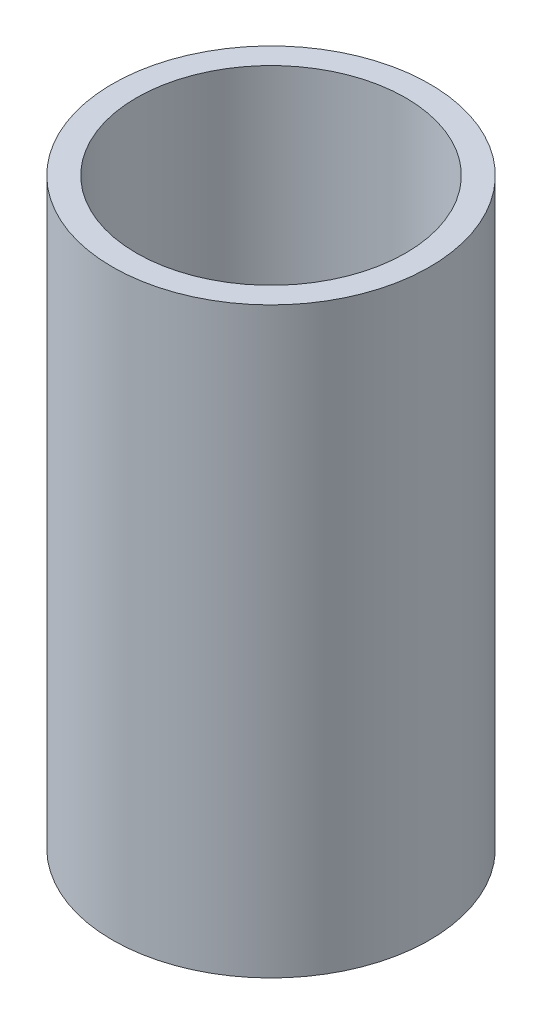
SolidWorks part; units mm, degrees
ref_plane "Front Plane" through (0, 0, 0) normal (0, 0, 1) x (1, 0, 0)
ref_plane "Top Plane" through (0, 0, 0) normal (0, 1, 0) x (1, 0, 0)
ref_plane "Right Plane" through (0, 0, 0) normal (1, 0, 0) x (0, 0, -1)
sketch "Sketch1" plane through (0, 0, 0) normal (0, 1, 0) x (1, 0, 0)
  circle A0 centre (0, 0) radius 45
  dimension "SLEEVE_OD" = 90
extrude "Boss-Extrude1" add sketch "Sketch1" along normal blind 165.384
sketch "Sketch2" plane through (0, 0, 0) normal (0, 1, 0) x (1, 0, 0)
  circle A0 centre (0, 0) radius 38.1856
  dimension "BORE_D" = 76.3711
extrude "Cut-Extrude1" cut sketch "Sketch2" along normal through all
chamfer "Chamfer1" distance 3.2107 angle 67.664 rebuild error yes
